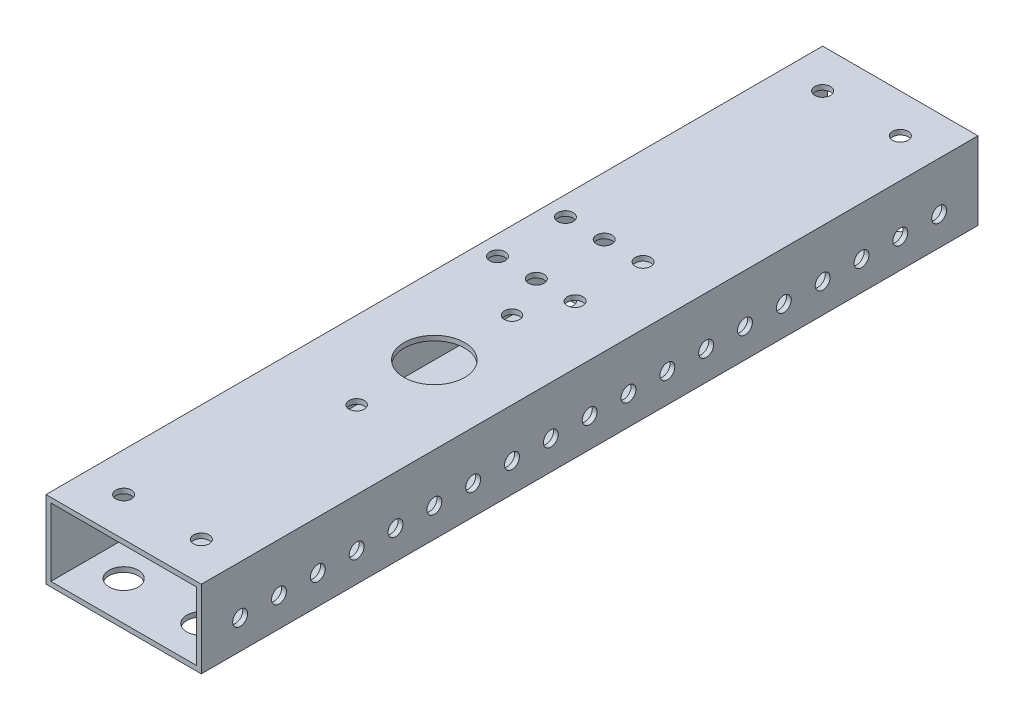
SolidWorks part; units mm, degrees
other "Markup1"
sketch "Sketch7" plane through (25.4, 12.7, -127) normal (0.9965, 0.0171, -0.0817) x (-0.082, 0.0128, -0.9966)
sketch "Sketch8" plane through (25.4, 12.7, -127) normal (0.9965, 0.0171, -0.0817) x (-0.082, 0.0128, -0.9966)
sketch "Sketch9" plane through (25.4, 12.7, -127) normal (0.9965, 0.0171, -0.0817) x (-0.082, 0.0128, -0.9966)
material "6061-T6 (SS)"
ref_plane "Front Plane" through (0, 0, 0) normal (0, 0, 1) x (1, 0, 0)
ref_plane "Top Plane" through (0, 0, 0) normal (0, 1, 0) x (1, 0, 0)
ref_plane "Right Plane" through (0, 0, 0) normal (1, 0, 0) x (0, 0, -1)
sketch "Sketch1" plane through (0, 0, 0) normal (0, 0, 1) x (1, 0, 0)
  line L0 (-23.8125, 11.1125) -> (23.8125, 11.1125)
  line L1 (-25.4, -12.7) -> (25.4, -12.7)
  line L2 (-25.4, -12.7) -> (-25.4, 12.7)
  line L3 (-25.4, 12.7) -> (25.4, 12.7)
  line L4 (25.4, -12.7) -> (25.4, 12.7)
  line L5 (-25.4, -12.7) -> (25.4, 12.7) construction
  line L6 (-25.4, 12.7) -> (25.4, -12.7) construction
  line L7 (23.8125, -11.1125) -> (23.8125, 11.1125)
  line L8 (-23.8125, -11.1125) -> (23.8125, -11.1125)
  line L9 (-23.8125, -11.1125) -> (-23.8125, 11.1125)
  point P0 (0, 0)
  dimension "D1" = 50.8
  dimension "D2" = 25.4
  dimension "D3" = 1.5875
extrude "Boss-Extrude1" add sketch "Sketch1" along normal mid plane 254
sketch "Sketch3" plane through (0, 12.7, 0) normal (0, 1, 0) x (1, 0, 0)
  line L0 (25.4, 127) -> (-25.4, 127) construction
  line L1 (25.4, -127) -> (-25.4, -127) construction
  line L3 (-25.4, -127) -> (-25.4, 127) construction
  line L4 (25.4, -127) -> (25.4, 127) construction
  circle A0 centre (-12.7, -114.3) radius 2.5527
  circle A1 centre (12.7, -114.3) radius 2.5527
  circle A2 centre (-12.7, 114.3) radius 2.5527
  circle A3 centre (12.7, 114.3) radius 2.5527
  dimension "D5" = 5.1054
  dimension "D1" = 12.7
  dimension "D2" = 12.7
  dimension "D3" = 12.7
  dimension "D4" = 12.7
  dimension "D6" = 25.4
  dimension "D7" = 25.4
  dimension "D8" = 12.7
  dimension "D9" = 12.7
  dimension "D10" = 12.7
  dimension "D11" = 12.7
extrude "Cut-Extrude1" cut sketch "Sketch3" against normal up to surface (1.5875 mm away) up to face at (0, 11.1125, 0)
sketch "Sketch5" plane through (0, -12.7, 0) normal (0, -1, 0) x (1, 0, 0)
  circle A0 centre (-12.7, -114.3) radius 2.5527 construction
  circle A1 centre (12.7, -114.3) radius 2.5527 construction
  circle A2 centre (12.7, 114.3) radius 2.5527 construction
  circle A3 centre (-12.7, 114.3) radius 2.5527 construction
  circle A4 centre (-12.7, -114.3) radius 2.5527
  circle A5 centre (12.7, -114.3) radius 2.5527
  circle A6 centre (12.7, 114.3) radius 2.5527
  circle A7 centre (-12.7, 114.3) radius 2.5527
  circle A8 centre (-12.7, 114.3) radius 4.7625
  circle A9 centre (12.7, 114.3) radius 4.7625
  circle A10 centre (12.7, -114.3) radius 4.7625
  circle A11 centre (-12.7, -114.3) radius 4.7625
  dimension "D1" = 9.525
extrude "Cut-Extrude2" cut sketch "Sketch5" against normal up to surface (1.5875 mm away) contours A10 A5 | A5 | A11 A4 | A4 | A6 | A9 A6 | A8 A7 | A7 region at (-12.7, -12.7, -114.3) region at (12.7, -12.7, -114.3) region at (12.7, -12.7, 114.3) region at (-12.7, -12.7, 114.3) region at (-17.3278, -12.7, 114.3) region at (8.0722, -12.7, 114.3) region at (8.0722, -12.7, -114.3) region at (-17.3278, -12.7, -114.3) up to face at (0, -11.1125, 0)
sketch "Sketch6" plane through (25.4, 0, 0) normal (1, 0, 0) x (0, 0, -1)
  line L0 (-127, -12.7) -> (-127, 12.7) construction
  line L1 (-127, -12.7) -> (127, -12.7) construction
  line L2 (0, 12.7) -> (0, -12.7) construction
  line L3 (-127, 12.7) -> (127, 12.7) construction
  circle A0 centre (-114.3, -3.175) radius 2.4384
  circle A1 centre (-101.6, -3.175) radius 2.4384
  circle A2 centre (-88.9, -3.175) radius 2.4384
  circle A3 centre (88.9, -3.175) radius 2.4384
  circle A4 centre (101.6, -3.175) radius 2.4384
  circle A5 centre (114.3, -3.175) radius 2.4384
  circle A6 centre (-76.2, -3.175) radius 2.4384
  circle A7 centre (-63.5, -3.175) radius 2.4384
  circle A8 centre (-50.8, -3.175) radius 2.4384
  circle A9 centre (-38.1, -3.175) radius 2.4384
  circle A10 centre (-25.4, -3.175) radius 2.4384
  circle A11 centre (-12.7, -3.175) radius 2.4384
  circle A12 centre (0, -3.175) radius 2.4384
  circle A13 centre (12.7, -3.175) radius 2.4384
  circle A14 centre (25.4, -3.175) radius 2.4384
  circle A15 centre (38.1, -3.175) radius 2.4384
  circle A16 centre (50.8, -3.175) radius 2.4384
  circle A17 centre (63.5, -3.175) radius 2.4384
  circle A18 centre (76.2, -3.175) radius 2.4384
  dimension "D1" = 4.8768
  dimension "D7" = 4.8768
  dimension "D2" = 12.7
  dimension "D3" = 9.525
  dimension "D4" = 12.7
  dimension "D5" = 12.7
  dimension "D6" = 12.7
  dimension "D8" = 9.525
  dimension "D10" = 12.7
  dimension "D9" = 13
extrude "Cut-Extrude3" cut sketch "Sketch6" against normal up to surface (1.5875 mm away) contours A5 | A4 | A3 | A0 | A1 | A2 | A6 | A7 | A8 | A9 | A10 | A11 | A12 L2 | L2 A12 | A13 | A14 | A15 | A16 | A17 | A18 | A12 region at (25.4, -3.175, -1.0349) region at (25.4, -3.175, 1.0349) region at (25.4, -3.175, 114.3) region at (25.4, -3.175, 101.6) region at (25.4, -3.175, 88.9) region at (25.4, -3.175, -88.9) region at (25.4, -3.175, -101.6) region at (25.4, -3.175, -114.3) region at (25.4, -3.175, 76.2) region at (25.4, -3.175, 63.5) region at (25.4, -3.175, 50.8) region at (25.4, -3.175, 38.1) region at (25.4, -3.175, 25.4) region at (25.4, -3.175, 12.7) region at (25.4, -3.175, -12.7) region at (25.4, -3.175, -25.4) region at (25.4, -3.175, -38.1) region at (25.4, -3.175, -50.8) region at (25.4, -3.175, -63.5) region at (25.4, -3.175, -76.2) up to face at (23.8125, 0, 0)
sketch "Sketch11" plane through (0, 12.7, 0) normal (0, 1, 0) x (1, 0, 0)
  line L0 (-25.4, -127) -> (-25.4, 127) construction
  line L2 (0, 0) -> (0, -50.8) construction
  line L3 (25.4, 127) -> (-25.4, 127) construction
  line L5 (-19.05, 36.5125) -> (6.35, 36.5125) construction
  line L6 (-19.05, 36.5125) -> (-19.05, 14.2875) construction
  line L7 (-19.05, 14.2875) -> (6.35, 14.2875) construction
  line L8 (6.35, 36.5125) -> (6.35, 14.2875) construction
  line L9 (-19.05, 36.5125) -> (6.35, 14.2875) construction
  line L10 (-19.05, 14.2875) -> (6.35, 36.5125) construction
  circle A0 centre (0, -25.4) radius 9.906
  circle A1 centre (0, 0) radius 2.4892
  circle A2 centre (0, -50.8) radius 2.4892
  circle A3 centre (6.35, 14.2875) radius 2.5527
  circle A4 centre (-19.05, 14.2875) radius 2.5527
  circle A5 centre (-19.05, 36.5125) radius 2.5527
  circle A6 centre (6.35, 36.5125) radius 2.5527
  circle A7 centre (-6.35, 14.2875) radius 2.5527
  circle A8 centre (-6.35, 36.5125) radius 2.5527
  point P2 (0, -25.4)
  point P8 (-6.35, 25.4)
  point P24 (0, 0)
  point P25 (0, 0)
  point P26 (0, 0)
  point P27 (0, 14.2875)
  point P28 (0, 0)
  point P29 (-5.0943, 36.5125)
  dimension "D1" = 19.812
  dimension "D3" = 4.9784
  dimension "D4" = 25.4
  dimension "D5" = 5.1054
  dimension "D6" = 25.4
  dimension "D7" = 22.225
  dimension "D2" = 152.4
  dimension "D8" = 101.6
  dimension "D9" = 6.35
extrude "Cut-Extrude4" cut sketch "Sketch11" against normal through all
